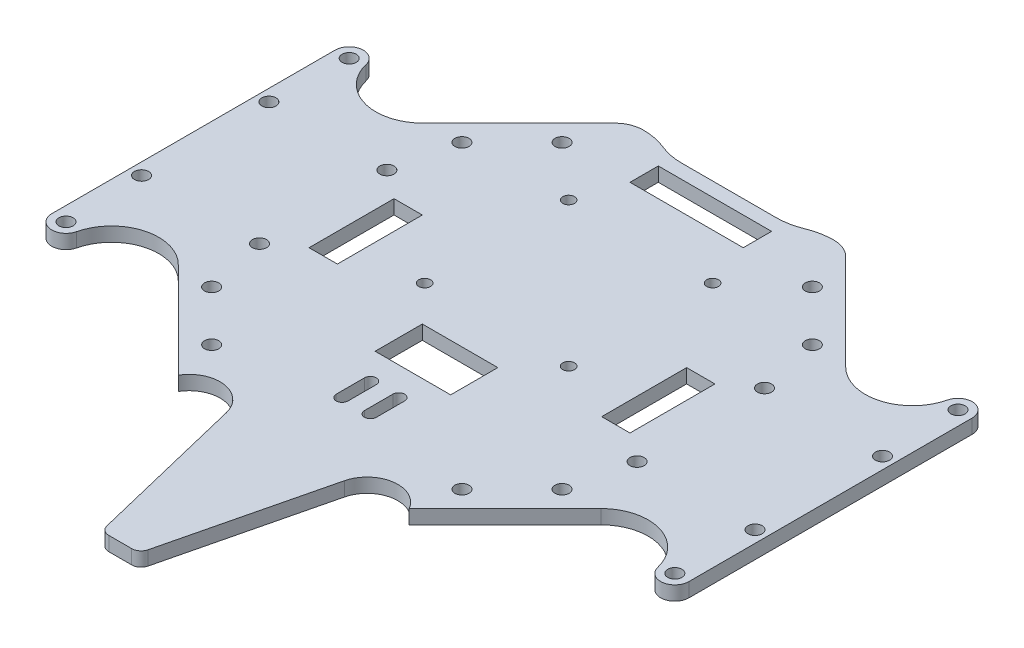
SolidWorks part; units mm, degrees
ref_plane "前视基准面" through (0, 0, 0) normal (0, 0, 1) x (1, 0, 0)
ref_plane "上视基准面" through (0, 0, 0) normal (0, 1, 0) x (1, 0, 0)
ref_plane "右视基准面" through (0, 0, 0) normal (1, 0, 0) x (0, 0, -1)
sketch "草图1" plane through (0, 0, 0) normal (0, 1, 0) x (1, 0, 0)
  line L0 (0, 79.9225) -> (0, -68.1747) construction
  line L1 (-93.1075, 0) -> (111.4791, 0) construction
  line L2 (-55.8728, 55.8728) -> (39.2533, -39.2533) construction
  line L3 (-19.318, 44.3216) -> (-45.661, 17.9787) construction
  line L4 (-12.5, -50) -> (-12.5, -81)
  line L5 (-67.5, 48) -> (67.5, 48)
  line L6 (-67.5, 48) -> (-67.5, -48)
  line L7 (-67.5, -48) -> (-14.5, -48)
  line L8 (67.5, 48) -> (67.5, -48)
  line L9 (-67.5, 48) -> (67.5, -48) construction
  line L10 (-67.5, -48) -> (67.5, 48) construction
  line L11 (-10.5, -83) -> (10.5, -83)
  line L12 (12.5, -81) -> (12.5, -50)
  line L13 (14.5, -48) -> (67.5, -48)
  circle A0 centre (-37.1231, 26.5165) radius 1.5
  circle A1 centre (-26.5165, 37.1231) radius 1.5
  circle A2 centre (26.5165, 37.1231) radius 1.5
  circle A3 centre (37.1231, 26.5165) radius 1.5
  circle A4 centre (37.1231, -26.5165) radius 1.5
  circle A5 centre (26.5165, -37.1231) radius 1.5
  circle A6 centre (-37.1231, -26.5165) radius 1.5
  circle A7 centre (-26.5165, -37.1231) radius 1.5
  arc A8 (-12.5, -50) -> (-14.5, -48) centre (-14.5, -50) ccw
  arc A9 (10.5, -83) -> (12.5, -81) centre (10.5, -81) ccw
  arc A10 (-12.5, -81) -> (-10.5, -83) centre (-10.5, -81) ccw
  arc A11 (14.5, -48) -> (12.5, -50) centre (14.5, -50) ccw
  point P25 (0, 0)
  point P38 (12.5, -83)
  point P41 (-12.5, -83)
  point P44 (12.5, -48)
  dimension "D3" = 3
  dimension "D11" = 2
  dimension "D12" = 2
  dimension "D1" = 45
  dimension "D2" = 45
  dimension "D4" = 15
  dimension "D5" = 7.5
  dimension "D6" = 135
  dimension "D7" = 96
  dimension "D8" = 25
  dimension "D9" = 12.5
  dimension "D10" = 35
extrude "凸台-拉伸1" add sketch "草图1" along normal blind 3
sketch "草图2" plane through (0, 3, 0) normal (0, 1, 0) x (1, 0, 0)
  line L0 (0, 63.5592) -> (0, -64.9484) construction
  line L1 (-71.5475, 0) -> (75.0978, 0) construction
  line L2 (-37.1231, -26.5165) -> (-26.5165, -37.1231) construction
  line L3 (-33.234, -15.5563) -> (-15.5563, -33.234) construction
  line L4 (-26.5481, -26.5481) -> (-35.1226, -35.1226) construction
  line L5 (-33.234, -15.5563) -> (-43.6511, -25.9734) construction
  line L6 (-15.25, 3.25) -> (15.25, -27.25) construction
  line L7 (15.25, 3.25) -> (-15.25, -27.25) construction
  line L8 (3, 33) -> (3, 27) construction
  line L9 (-17.5, 5.5) -> (17.5, 5.5) construction
  line L10 (-17.5, 5.5) -> (-17.5, -29.5) construction
  line L11 (-17.5, -29.5) -> (17.5, -29.5) construction
  line L12 (17.5, 5.5) -> (17.5, -29.5) construction
  line L13 (-17.5, 5.5) -> (17.5, -29.5) construction
  line L14 (-17.5, -29.5) -> (17.5, 5.5) construction
  line L15 (4.25, 33) -> (4.25, 27) construction
  line L16 (1.75, 33) -> (1.75, 27) construction
  line L17 (-3, 33) -> (-3, 27) construction
  line L18 (-4.25, 33) -> (-4.25, 27) construction
  line L19 (-1.75, 33) -> (-1.75, 27) construction
  line L20 (3, -33) -> (3, -27) construction
  line L21 (4.25, -33) -> (4.25, -27)
  line L22 (1.75, -33) -> (1.75, -27)
  line L23 (-3, -33) -> (-3, -27) construction
  line L24 (-4.25, -33) -> (-4.25, -27)
  line L25 (-1.75, -33) -> (-1.75, -27)
  line L27 (-8, -11) -> (8, -11)
  line L28 (-8, -11) -> (-8, -21)
  line L29 (-8, -21) -> (8, -21)
  line L30 (8, -11) -> (8, -21)
  line L31 (-8, -11) -> (8, -21) construction
  line L32 (-8, -21) -> (8, -11) construction
  circle A0 centre (-40, 13.5) radius 1.5
  circle A1 centre (-40, -13.5) radius 1.5
  circle A3 centre (-15.25, 3.25) radius 1.25 construction
  circle A4 centre (15.25, 3.25) radius 1.25 construction
  circle A5 centre (15.25, -27.25) radius 1.25 construction
  circle A6 centre (-15.25, -27.25) radius 1.25 construction
  circle A7 centre (-65, 13.5) radius 1.5
  circle A8 centre (-65, -13.5) radius 1.5
  circle A13 centre (40, -13.5) radius 1.5
  circle A14 centre (40, 13.5) radius 1.5
  arc A15 (4.25, 33) -> (1.75, 33) centre (3, 33) ccw construction
  arc A16 (1.75, 27) -> (4.25, 27) centre (3, 27) ccw construction
  arc A17 (-4.25, 33) -> (-1.75, 33) centre (-3, 33) cw construction
  arc A18 (-1.75, 27) -> (-4.25, 27) centre (-3, 27) cw construction
  circle A19 centre (65, -13.5) radius 1.5
  circle A20 centre (65, 13.5) radius 1.5
  arc A21 (4.25, -33) -> (1.75, -33) centre (3, -33) cw
  arc A22 (1.75, -27) -> (4.25, -27) centre (3, -27) cw
  arc A23 (-4.25, -33) -> (-1.75, -33) centre (-3, -33) ccw
  arc A24 (-1.75, -27) -> (-4.25, -27) centre (-3, -27) ccw
  circle A25 centre (-15.25, 27.25) radius 1.25
  circle A26 centre (15.25, 27.25) radius 1.25
  circle A27 centre (15.25, -3.25) radius 1.25
  circle A28 centre (-15.25, -3.25) radius 1.25
  point P27 (0, -12)
  point P41 (3, 30)
  point P48 (-3, 30)
  point P57 (3, -30)
  point P66 (-3, -30)
  point P81 (0, -16)
  dimension "D1" = 3
  dimension "D6" = 2.5
  dimension "D19" = 2.5
  dimension "D20" = 6
  dimension "D21" = 30
  dimension "D24" = 3
  dimension "D2" = 27
  dimension "D3" = 13.5
  dimension "D4" = 25
  dimension "D5" = 25
  dimension "D7" = 30.5
  dimension "D8" = 30.5
  dimension "D9" = 15.25
  dimension "D10" = 30.5
  dimension "D11" = 10.5
  dimension "D12" = 25
  dimension "D13" = 7.5
  dimension "D14" = 12.5
  dimension "D15" = 40
  dimension "D16" = 35
  dimension "D17" = 35
  dimension "D18" = 12
  dimension "D22" = 3
  dimension "D23" = 27
  dimension "D25" = 10
  dimension "D26" = 16
  dimension "D27" = 16
extrude "切除-拉伸1" cut sketch "草图2" against normal blind 31
sketch "草图3" plane through (0, 3, 0) normal (0, 1, 0) x (1, 0, 0)
  line L0 (0, 0) -> (-95.846, 0) construction
  line L1 (0, 0) -> (0, 65.2529) construction
  line L2 (-67.5, 16.5) -> (-37.5, 16.5) construction
  line L3 (-37.5, 16.5) -> (-37.5, -16.5) construction
  line L4 (-37.5, -16.5) -> (-67.5, -16.5) construction
  line L5 (-67.5, -16.5) -> (-67.5, 16.5) construction
  line L6 (67.5, 48) -> (-67.5, 48) construction
  line L7 (-12, 43) -> (12, 43)
  line L8 (-12, 43) -> (-12, 37)
  line L9 (-12, 37) -> (12, 37)
  line L10 (12, 43) -> (12, 37)
  line L11 (-12, 43) -> (12, 37) construction
  line L12 (-12, 37) -> (12, 43) construction
  line L17 (34, -9) -> (28, -9)
  line L18 (-34, 9) -> (-28, 9)
  line L19 (-34, 9) -> (-34, -9)
  line L20 (-34, -9) -> (-28, -9)
  line L21 (-28, 9) -> (-28, -9)
  line L22 (-34, 9) -> (-28, -9) construction
  line L23 (-34, -9) -> (-28, 9) construction
  line L24 (28, 9) -> (28, -9)
  line L25 (34, 9) -> (34, -9)
  line L26 (34, 9) -> (28, 9)
  circle A0 centre (-40, 13.5) radius 1.5 construction
  circle A1 centre (-65, 13.5) radius 1.5 construction
  point P12 (0, 40)
  point P23 (-31, 0)
  dimension "D4" = 40
  dimension "D5" = 65
  dimension "D1" = 30
  dimension "D2" = 33
  dimension "D3" = 16.5
  dimension "D6" = 37.5
  dimension "D7" = 6
  dimension "D8" = 5
  dimension "D9" = 24
  dimension "D10" = 31
  dimension "D11" = 6
  dimension "D12" = 18
extrude "切除-拉伸2" cut sketch "草图3" against normal blind 10
sketch "草图5" plane through (0, 3, 0) normal (0, 1, 0) x (1, 0, 0)
  line L0 (-26.5165, 37.1231) -> (-37.1231, 26.5165) construction
  line L1 (-24.468, 46.2426) -> (-44.7802, 25.9305)
  line L2 (67.5, 48) -> (-67.5, 48) construction
  line L3 (0, 0) -> (0, 54.7575) construction
  line L4 (0, 0) -> (70.8766, 0) construction
  line L5 (-67.5, 48) -> (-67.5, -48) construction
  line L6 (67.5, 48) -> (-20.2254, 48) construction
  line L7 (-20.2254, 48) -> (-67.5, 48)
  line L8 (-67.5, 48) -> (-67.5, 30)
  line L9 (67.5, 48) -> (67.5, 30)
  line L10 (24.468, 46.2426) -> (44.7802, 25.9305)
  line L11 (20.2254, 48) -> (67.5, 48)
  line L12 (67.5, -48) -> (67.5, -30)
  line L13 (20.2254, -48) -> (67.5, -48)
  line L14 (24.468, -46.2426) -> (44.7802, -25.9305)
  line L15 (-20.2254, -48) -> (-67.5, -48)
  line L16 (-67.5, -48) -> (-67.5, -30)
  line L17 (-24.468, -46.2426) -> (-44.7802, -25.9305)
  circle A0 centre (-26.5165, 37.1231) radius 1.5 construction
  circle A1 centre (-64.5, 30) radius 1.5
  circle A2 centre (-64.5, -30) radius 1.5 construction
  circle A3 centre (-64.5, 30) radius 3 construction
  arc A4 (-61.5811, 30.6927) -> (-44.7802, 25.9305) centre (-51.8513, 33.0016) ccw
  arc A5 (-20.2254, 48) -> (-24.468, 46.2426) centre (-20.2254, 42) ccw
  arc A6 (-67.5, 30) -> (-61.5811, 30.6927) centre (-64.5, 30) cw
  circle A7 centre (64.5, 30) radius 1.5
  arc A8 (61.5811, 30.6927) -> (44.7802, 25.9305) centre (51.8513, 33.0016) cw
  arc A9 (67.5, 30) -> (61.5811, 30.6927) centre (64.5, 30) ccw
  arc A10 (20.2254, 48) -> (24.468, 46.2426) centre (20.2254, 42) cw
  circle A11 centre (64.5, -30) radius 1.5
  arc A12 (20.2254, -48) -> (24.468, -46.2426) centre (20.2254, -42) ccw
  arc A13 (61.5811, -30.6927) -> (44.7802, -25.9305) centre (51.8513, -33.0016) ccw
  arc A14 (67.5, -30) -> (61.5811, -30.6927) centre (64.5, -30) cw
  circle A15 centre (-64.5, -30) radius 1.5
  arc A16 (-67.5, -30) -> (-61.5811, -30.6927) centre (-64.5, -30) ccw
  arc A17 (-61.5811, -30.6927) -> (-44.7802, -25.9305) centre (-51.8513, -33.0016) cw
  arc A18 (-20.2254, -48) -> (-24.468, -46.2426) centre (-20.2254, -42) cw
  dimension "D2" = 3
  dimension "D6" = 6
  dimension "D7" = 10
  dimension "D8" = 6
  dimension "D1" = 5
  dimension "D3" = 3
  dimension "D5" = 30
extrude "切除-拉伸3" cut sketch "草图5" against normal blind 10
sketch "草图6" plane through (0, 3, 0) normal (0, 1, 0) x (1, 0, 0)
  line L0 (-10, 46) -> (10, 46)
  line L1 (0, 0) -> (0, 60.9736) construction
  line L2 (20.2254, 48) -> (-20.2254, 48) construction
  line L3 (20.2254, 48) -> (-20.2254, 48) construction
  line L4 (-20.2254, 48) -> (20.2254, 48) construction
  line L5 (-20.2254, 48) -> (-20.2254, 49)
  line L6 (-20.2254, 49) -> (20.2254, 49)
  line L7 (20.2254, 49) -> (20.2254, 48)
  line L10 (0, 0) -> (0, -99.7402) construction
  line L15 (-4.3711, -81.472) -> (-12.5, -48)
  line L18 (-2.4276, -83) -> (2.4276, -83)
  line L19 (-10.5, -83) -> (10.5, -83) construction
  line L21 (-24.468, -84) -> (24.468, -84)
  line L22 (4.3711, -81.472) -> (12.5, -48)
  line L23 (12.5, -81) -> (12.5, -50) construction
  line L24 (14.5, -48) -> (20.2254, -48) construction
  line L25 (-24.468, -46.2426) -> (-24.468, -84)
  line L26 (24.468, -46.2426) -> (24.468, -84)
  arc A0 (-20.2254, 48) -> (-24.468, 46.2426) centre (-20.2254, 42) ccw construction
  arc A1 (-20.2254, 48) -> (-24.468, 46.2426) centre (-20.2254, 42) ccw construction
  arc A2 (-20.2254, 48) -> (-15, 46.978) centre (-20.2254, 34.131) cw
  arc A3 (-15, 46.978) -> (-10, 46) centre (-10, 59.2707) ccw
  arc A4 (15, 46.978) -> (10, 46) centre (10, 59.2707) cw
  arc A5 (20.2254, 48) -> (15, 46.978) centre (20.2254, 34.131) ccw
  arc A9 (20.2254, -48) -> (24.468, -46.2426) centre (20.2254, -42) ccw construction
  arc A10 (20.2254, -48) -> (24.468, -46.2426) centre (20.2254, -42) ccw construction
  arc A13 (-24.468, -46.2426) -> (-20.2254, -48) centre (-20.2254, -42) ccw construction
  arc A14 (-24.468, -46.2426) -> (-20.2254, -48) centre (-20.2254, -42) ccw construction
  arc A15 (-4.3711, -81.472) -> (-2.4276, -83) centre (-2.4276, -81) ccw
  arc A16 (2.4276, -83) -> (4.3711, -81.472) centre (2.4276, -81) ccw
  arc A17 (12.5, -48) -> (24.468, -46.2426) centre (18.8391, -49.5395) cw
  arc A18 (-12.5, -48) -> (-24.468, -46.2426) centre (-18.8391, -49.5395) ccw
  point P40 (-4, -83)
  point P43 (4, -83)
  dimension "D6" = 2
  dimension "D7" = 2
  dimension "D1" = 20
  dimension "D2" = 1
  dimension "D3" = 2
  dimension "D4" = 5
  dimension "D5" = 8
  dimension "D8" = 1
extrude "切除-拉伸4" cut sketch "草图6" against normal blind 3
